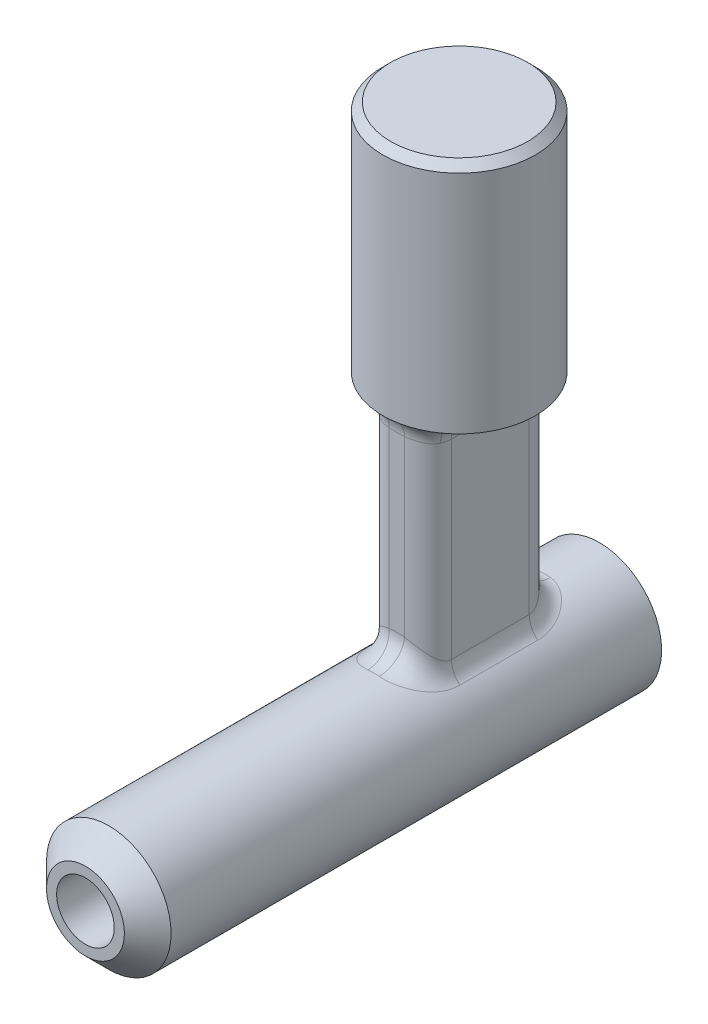
SolidWorks part; units mm, degrees
ref_plane "Front Plane" through (0, 0, 0) normal (0, 0, 1) x (1, 0, 0)
ref_plane "Top Plane" through (0, 0, 0) normal (0, 1, 0) x (1, 0, 0)
ref_plane "Right Plane" through (0, 0, 0) normal (1, 0, 0) x (0, 0, -1)
sketch "Sketch1" plane through (0, 0, 0) normal (0, 0, 1) x (1, 0, 0)
  circle A0 centre (0, 0) radius 4
  dimension "D1" = 8
extrude "Boss-Extrude1" add sketch "Sketch1" along normal blind 18
sketch "Sketch2" plane through (0, 0, 18) normal (0, 0, 1) x (1, 0, 0)
  circle A0 centre (0, 0) radius 1.85
  circle A2 centre (0, 0) radius 3.3
  dimension "D1" = 3.7
  dimension "D3" = 6.6
extrude "Cut-Extrude1" cut sketch "Sketch2" against normal through all contours A0 region at (0, 0, 18)
extrude "Cut-Extrude2" cut sketch "Sketch2<3>" along normal blind 2 from surface contours A0 region at (-3.2067, 0, 18) starting at face at (1.85, 0, 0)
sketch "Sketch2<3>" plane through (0, 0, 18) normal (0, 0, 1) x (1, 0, 0) same geometry as "Sketch2"
sketch "Sketch6" plane through (0, 0, 0) normal (0, 0, -1) x (-1, 0, 0)
  circle A0 centre (0, 0) radius 3.3 construction
  circle A1 centre (0, 0) radius 4
  circle A2 centre (0, 0) radius 4
  circle A3 centre (0, 0) radius 3.3
  dimension "D1" = 0
extrude "Boss-Extrude4" add sketch "Sketch6" along normal blind 15
sketch "Sketch4" plane through (0, 0, 0) normal (0, 1, 0) x (1, 0, 0)
  line L1 (-2, 10) -> (2, 10)
  line L2 (-2, 10) -> (-2, 2)
  line L3 (-2, 2) -> (2, 2)
  line L4 (2, 10) -> (2, 2)
  point P4 (0, 10)
  dimension "D1" = 8
  dimension "D2" = 2
  dimension "D3" = 4
extrude "Boss-Extrude2" add sketch "Sketch4" against normal up to surface (14.5359 mm away) from offset 18 up to face at (4, 0, 18)
sketch "Sketch5" plane through (0, 18, 0) normal (0, 1, 0) x (1, 0, 0)
  line L0 (2, 2) -> (2, 10) construction
  circle A0 centre (0, 6) radius 4.9
  point P2 (2, 6)
  dimension "D1" = 9.8
extrude "Boss-Extrude3" add sketch "Sketch5" along normal blind 15
fillet "Fillet1" radius 1.5 4 edges at (-2, 10.7321, -10) (-2, 10.7321, -2) (2, 10.7321, -2) (2, 10.7321, -10)
fillet "Fillet3" radius 1.5 14 edges at (-1.5607, 18, -9.5607) (1.5607, 18, -9.5607) (2, 18, -6) (1.5607, 18, -2.4393) (-1.5607, 18, -2.4393) (-1.728, 3.6075, -9.3614) (1.4157, 3.7411, -9.6881) (2, 3.4641, -6) (1.728, 3.6075, -2.6386) (0, 4, -2) (-1.4157, 3.7411, -2.3119) (-2, 18, -6) (-2, 3.4641, -6) (0, 4, -10)
chamfer "Chamfer3" distance 0.5 angle 45 1 edges at (0, 33, -1.1)
chamfer "Chamfer5" distance 1.5 angle 45 1 edges at (4, 0, 18)
